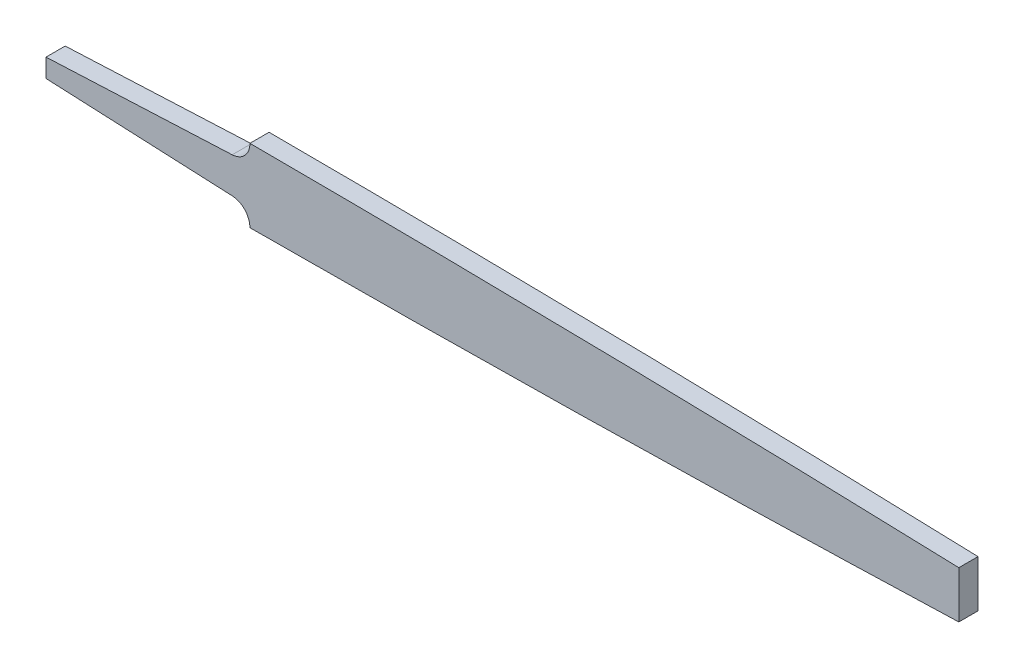
SolidWorks part; units mm, degrees
ref_plane "Front Plane" through (0, 0, 0) normal (0, 0, 1) x (1, 0, 0)
ref_plane "Top Plane" through (0, 0, 0) normal (0, 1, 0) x (1, 0, 0)
ref_plane "Right Plane" through (0, 0, 0) normal (1, 0, 0) x (0, 0, -1)
ref_axis "Axis1" through (-33.0333, 0, 0) along (1, 0, 0)
ref_axis "Axis2" through (0, 24.5224, 0) along (0, -1, 0)
ref_axis "Axis3" through (0, 0, -30.7663) along (0, 0, 1)
sketch "Sketch1" plane through (0, 0, 0) normal (0, 0, 1) x (1, 0, 0)
  line L0 (-98.5, 0) -> (98.5, 0) construction
  line L1 (-98.5, -2) -> (-98.5, 2)
  line L2 (-98.5, 2) -> (-58.3175, 3.835)
  line L3 (-54.5, 7.8308) -> (-54.5, 7.885)
  line L4 (98.5, 5.075) -> (98.5, -5.075)
  line L5 (-54.5, -7.8308) -> (-54.5, -7.885)
  line L6 (-98.5, -2) -> (-58.3175, -3.835)
  arc A0 (-54.5, -7.8308) -> (-58.3175, -3.835) centre (-58.5, -7.8308) ccw
  arc A1 (-58.3175, 3.835) -> (-54.5, 7.8308) centre (-58.5, 7.8308) ccw
  spline S0 degree 2 poles (-54.5, 7.885) (22.0289, 7.6807) (98.5, 5.075) knots 0 0 0 1 1 1
  spline S1 degree 2 poles (-54.5, -7.885) (22.0289, -7.6807) (98.5, -5.075) knots 0 0 0 1 1 1
  point P2 (0, 0)
  point P14 (77.462, 5.7464)
  point P15 (-54.5, 3.7548)
  point P18 (-54.5, -4.0093)
  point P21 (-54.5, 4.0093)
  dimension "D6" = 4
  dimension "D1" = 197
  dimension "D2" = 2
  dimension "D3" = 44
  dimension "D4" = 7.885
  dimension "D5" = 5.075
  dimension "D7" = 3.835
extrude "Boss-Extrude1" add sketch "Sketch1" along normal blind 2.07 and the other way blind 2.07
